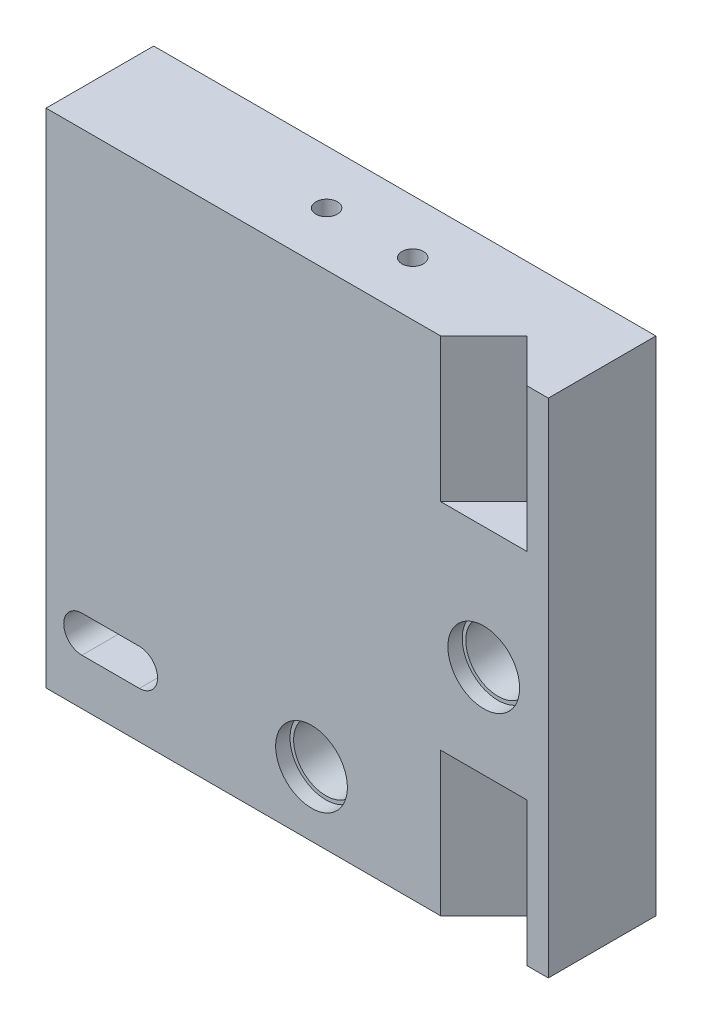
SolidWorks part; units mm, degrees
ref_plane "Front Plane" through (0, 0, 0) normal (0, 0, 1) x (1, 0, 0)
ref_plane "Top Plane" through (0, 0, 0) normal (0, 1, 0) x (1, 0, 0)
ref_plane "Right Plane" through (0, 0, 0) normal (1, 0, 0) x (0, 0, -1)
sketch "Sketch1" plane through (0, 0, 0) normal (0, 0, 1) x (1, 0, 0)
  line L1 (-17.7337, 13.9901) -> (17.2663, 13.9901)
  line L2 (-17.7337, 13.9901) -> (-17.7337, -21.0099)
  line L3 (-17.7337, -21.0099) -> (17.2663, -21.0099)
  line L4 (17.2663, 13.9901) -> (17.2663, -21.0099)
  dimension "D1" = 35
  dimension "D2" = 35
extrude "Boss-Extrude1" add sketch "Sketch1" along normal blind 7.5
sketch "Sketch2" plane through (0, 0, 0) normal (0, 0, -1) x (-1, 0, 0)
  line L0 (17.7337, 2.9901) -> (-6.2663, 2.9901)
  line L1 (17.7337, 13.9901) -> (17.7337, -21.0099) construction
  line L2 (-6.2663, 2.9901) -> (-6.2663, -10.0099)
  line L3 (-6.2663, -10.0099) -> (17.7337, -10.0099)
  line L4 (-17.2663, 13.9901) -> (17.7337, 13.9901) construction
  line L6 (-17.2663, -21.0099) -> (-17.2663, 13.9901) construction
  line L7 (17.7337, 2.9901) -> (17.7337, -10.0099)
  dimension "D1" = 13
  dimension "D2" = 11
  dimension "D3" = 11
extrude "Cut-Extrude2" cut sketch "Sketch2" against normal blind 5
sketch "Sketch4" plane through (0, 0, 7.5) normal (0, 0, 1) x (1, 0, 0)
  line L0 (-17.7337, 13.9901) -> (-17.7337, -21.0099) construction
  line L1 (-17.7337, -21.0099) -> (17.2663, -21.0099) construction
  line L3 (-11.2337, -15.2399) -> (-15.2337, -15.2399)
  line L5 (-11.2337, -17.7799) -> (-15.2337, -17.7799)
  line L7 (-11.2337, -15.2399) -> (-15.2337, -17.7799) construction
  line L8 (-11.2337, -17.7799) -> (-15.2337, -15.2399) construction
  arc A0 (-15.2337, -15.2399) -> (-15.2337, -17.7799) centre (-15.2337, -16.5099) ccw
  arc A1 (-11.2337, -15.2399) -> (-11.2337, -17.7799) centre (-11.2337, -16.5099) cw
  point P0 (-13.2337, -16.5099)
  dimension "D3" = 4
  dimension "D1" = 4.5
  dimension "D2" = 4.5
  dimension "D4" = 2.54
sketch "Sketch5" plane through (0, 0, 7.5) normal (0, 0, 1) x (1, 0, 0)
  line L0 (-17.7337, -21.0099) -> (17.2663, -21.0099) construction
  line L1 (17.2663, -21.0099) -> (17.2663, 13.9901) construction
  circle A0 centre (12.7663, -4.5099) radius 2.5
  circle A1 centre (0.7663, -16.5099) radius 2.5
  dimension "D5" = 5
  dimension "D6" = 5
  dimension "D1" = 16.5
  dimension "D2" = 16.5
  dimension "D3" = 4.5
  dimension "D4" = 4.5
sketch "Sketch10" plane through (0, 13.9901, 0) normal (0, 1, 0) x (1, 0, 0)
  line L0 (17.2663, -7.5) -> (17.2663, 0) construction
  line L1 (17.2663, 0) -> (-17.7337, 0) construction
  line L2 (17.2663, -7.5) -> (-17.7337, -7.5) construction
  circle A0 centre (4.0663, -3.75) radius 0.75
  circle A1 centre (-1.9337, -3.75) radius 0.75
  dimension "D1" = 13.2
  dimension "D2" = 1.5
  dimension "D3" = 1.5
  dimension "D4" = 3.75
  dimension "D5" = 3.75
  dimension "D6" = 6
extrude "Cut-Extrude7" cut sketch "Sketch10" against normal blind 7
extrude "Cut-Extrude11" cut sketch "Sketch5" against normal blind 1
sketch "Sketch11" plane through (0, 0, 6.5) normal (0, 0, 1) x (1, 0, 0)
  circle A0 centre (0.7663, -16.5099) radius 2.25
  circle A1 centre (12.7663, -4.5099) radius 2.25
  dimension "D1" = 4.5
  dimension "D2" = 4.5
extrude "Cut-Extrude12" cut sketch "Sketch11" against normal blind 5
sketch "Sketch13" plane through (0, -21.0099, 0) normal (0, -1, 0) x (1, 0, 0)
  line L0 (9.7663, 7.5) -> (12.7663, 4.5)
  line L1 (-17.7337, 7.5) -> (17.2663, 7.5) construction
  line L2 (12.7663, 4.5) -> (15.7663, 7.5)
  line L3 (17.2663, 7.5) -> (17.2663, 0) construction
  line L4 (9.7663, 7.5) -> (15.7663, 7.5)
  dimension "D1" = 3
  dimension "D2" = 135
  dimension "D3" = 4.5
extrude "Cut-Extrude13" cut sketch "Sketch13" against normal blind 10
sketch "Sketch15" plane through (0, 13.9901, 0) normal (0, 1, 0) x (1, 0, 0)
  line L0 (9.7663, -7.5) -> (12.7663, -4.5)
  line L1 (17.2663, -7.5) -> (-17.7337, -7.5) construction
  line L2 (12.7663, -4.5) -> (15.7663, -7.5)
  line L3 (9.7663, -7.5) -> (15.7663, -7.5)
  dimension "D1" = 0
  dimension "D2" = 0
  dimension "D3" = 0
extrude "Cut-Extrude14" cut sketch "Sketch15" against normal blind 10
extrude "Cut-Extrude15" cut sketch "Sketch4" against normal blind 4
